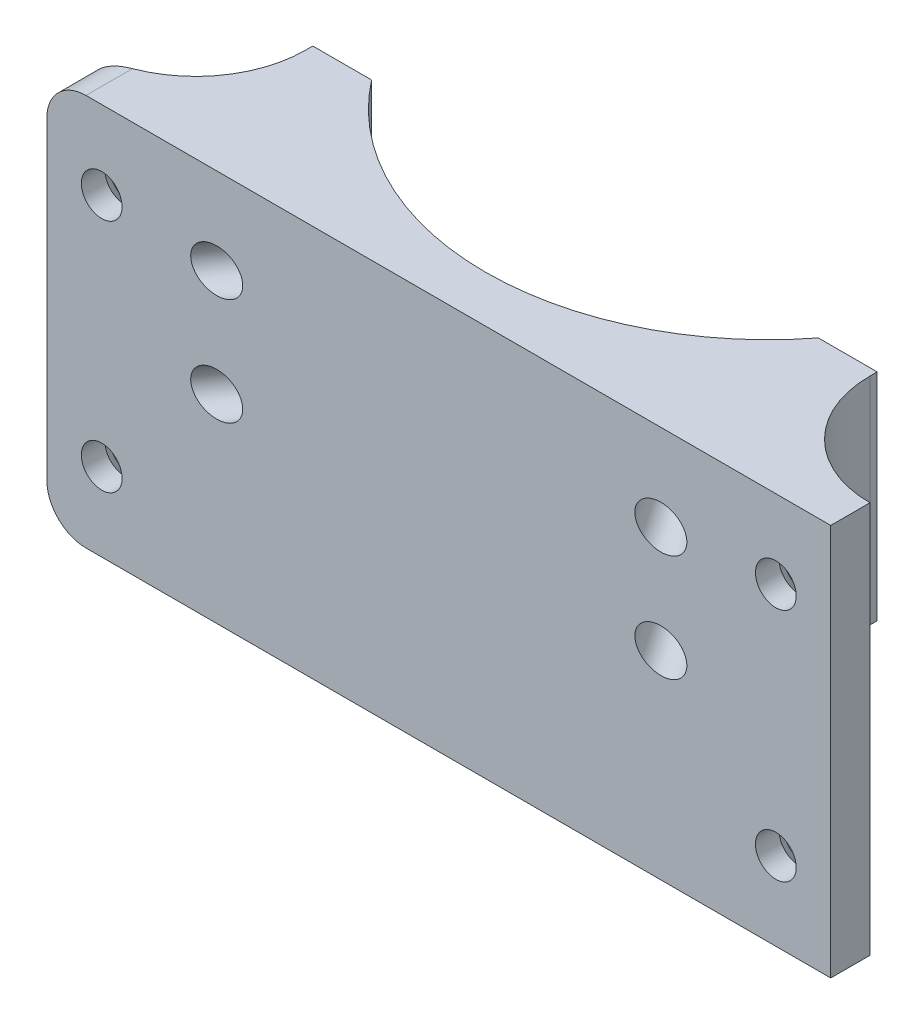
SolidWorks part; units mm, degrees
ref_plane "Front Plane" through (0, 0, 0) normal (0, 0, 1) x (1, 0, 0)
ref_plane "Top Plane" through (0, 0, 0) normal (0, 1, 0) x (1, 0, 0)
ref_plane "Right Plane" through (0, 0, 0) normal (1, 0, 0) x (0, 0, -1)
sketch "Sketch1" plane through (0, 0, 0) normal (0, 1, 0) x (1, 0, 0)
  line L0 (-28.5, -22.0761) -> (-36, -22.0761)
  line L1 (-36, -22.0761) -> (-36, -42)
  line L2 (-36, -42) -> (36, -42)
  line L4 (28.5, -22.0761) -> (36, -22.0761)
  line L5 (36, -22.0761) -> (36, -42)
  circle A0 centre (0, 0) radius 36 construction
  arc A1 (-28.5, -22.0761) -> (28.5, -22.0761) centre (0, 0) ccw
  dimension "D1" = 72
  dimension "D2" = 0.05
  dimension "D3" = 42
  dimension "D4" = 7.5
extrude "Boss-Extrude1" add sketch "Sketch1" along normal blind 27.5
sketch "Sketch2" plane through (0, 0, 0) normal (0, 1, 0) x (1, 0, 0)
  line L0 (0, 0) -> (0, -42) construction
  line L1 (-36, -42) -> (36, -42) construction
  line L2 (0, 0) -> (-20.1589, -29.8868) construction
  arc A0 (-28.5, -22.0761) -> (28.5, -22.0761) centre (0, 0) ccw construction
  dimension "D1" = 34
ref_plane "Plane1" through (-20.1589, 0, 29.8868) normal (0.5592, 0, -0.829) x (-0.829, 0, -0.5592)
ref_plane "Plane2" through (-21.8365, 0, 32.3739) normal (0.5592, 0, -0.829) x (-0.829, 0, -0.5592)
sketch "Sketch6" plane through (0, 0, 42) normal (0, 0, 1) x (1, 0, 0)
  line L0 (-36, 27.5) -> (36, 27.5) construction
  line L1 (-50, 27.5) -> (50, 27.5)
  line L2 (-50, 27.5) -> (-50, -22.5)
  line L3 (-50, -22.5) -> (50, -22.5)
  line L4 (50, 27.5) -> (50, -22.5)
  line L5 (-50, 27.5) -> (50, -22.5) construction
  line L6 (-50, -22.5) -> (50, 27.5) construction
  point P0 (0, 2.5)
  dimension "D1" = 100
  dimension "D2" = 50
extrude "Boss-Extrude2" add sketch "Sketch6" against normal blind 5
fillet "Fillet1" radius 14 3 edges at (-36, 13.75, 37) (0, 0, 37) (36, 13.75, 37)
sketch "Sketch3" plane through (-21.8365, 0, 32.3739) normal (0.5592, 0, -0.829) x (-0.829, 0, -0.5592)
  line L0 (-35.9723, 0) -> (-35.8753, 0) construction
  circle A0 centre (0, 2.829) radius 2.75
  circle A1 centre (0, 16.4756) radius 2.75
  dimension "D1" = 5.5
  dimension "D2" = 2.829
  dimension "D3" = 16.4756
extrude "Cut-Extrude3" cut sketch "Sketch3" against normal blind 27.5
hole_wizard "CSK for M2.5 Flat Head Machine Screw1" positions "Sketch4" profile "Sketch5" countersink size "M2.5" standard "ANSI Metric"
sketch "Sketch4" plane through (-21.8365, 0, 32.3739) normal (-0.5592, 0, 0.829) x (0.829, 0, 0.5592)
  circle A0 centre (0, 2.829) radius 2.75 construction
  point P0 (0, 16.4756)
  point P3 (0, 2.829)
sketch "Sketch5" plane through (-21.8365, 16.4756, 32.3739) normal (0, 1, 0) x (0.829, 0, 0.5592)
  line L0 (0, 0) -> (0, 7.8712)
  line L1 (0, 7.8712) -> (1.45, 7)
  line L2 (1.45, 7) -> (1.45, 1.3)
  line L3 (1.45, 1.3) -> (2.75, 0)
  line L5 (2.75, 0) -> (0, 0)
  line L6 (-1.45, 1.3) -> (-2.75, 0) construction
  line L10 (0, 7.8712) -> (-1.45, 7) construction
  line L11 (0, -6.35) -> (0, 107.95) construction
  dimension "Hole Dia." = 2.9
  dimension "Hole Depth" = 7
  dimension "Near C'Sink Dia." = 5.5
  dimension "Near C'Sink Angle" = 90
  dimension "Drill Angle" = 118
mirror "Mirror1" about plane through (0, 0, 0) normal (1, 0, 0) of "CSK for M2.5 Flat Head Machine Screw1", "Cut-Extrude3"
sketch "Sketch7" plane through (0, 0, 37) normal (0, 0, -1) x (-1, 0, 0)
  line L0 (0, 0) -> (0, -22.5) construction
  line L1 (50, -22.5) -> (-50, -22.5) construction
  line L2 (-43, 27.5) -> (-43, -22.5) construction
  line L3 (-36, 27.5) -> (-50, 27.5) construction
  circle A0 centre (-43, 17.5) radius 4.75
  circle A1 centre (-43, -12.5) radius 4.75
  circle A2 centre (43, -12.5) radius 4.75
  circle A3 centre (43, 17.5) radius 4.75
  dimension "D1" = 9.5
  dimension "D2" = 10
  dimension "D3" = 10
extrude "Cut-Extrude4" cut sketch "Sketch7" along normal through all
sketch "Sketch8" plane through (0, 0, 37) normal (0, 0, -1) x (-1, 0, 0)
  circle A0 centre (-43, 17.5) radius 2.6
  circle A1 centre (-43, -12.5) radius 2.6
  circle A2 centre (43, 17.5) radius 2.6
  circle A3 centre (43, -12.5) radius 2.6
  dimension "D1" = 5.2
extrude "Cut-Extrude5" cut sketch "Sketch8" against normal through all
chamfer "Chamfer1" distance 2 angle 45 4 edges at (-45.6, -12.5, 37) (-45.6, 17.5, 37) (40.4, -12.5, 37) (40.4, 17.5, 37)
fillet "Fillet3" radius 5 2 edges at (-50, 27.5, 39.5) (-50, -22.5, 39.5)
